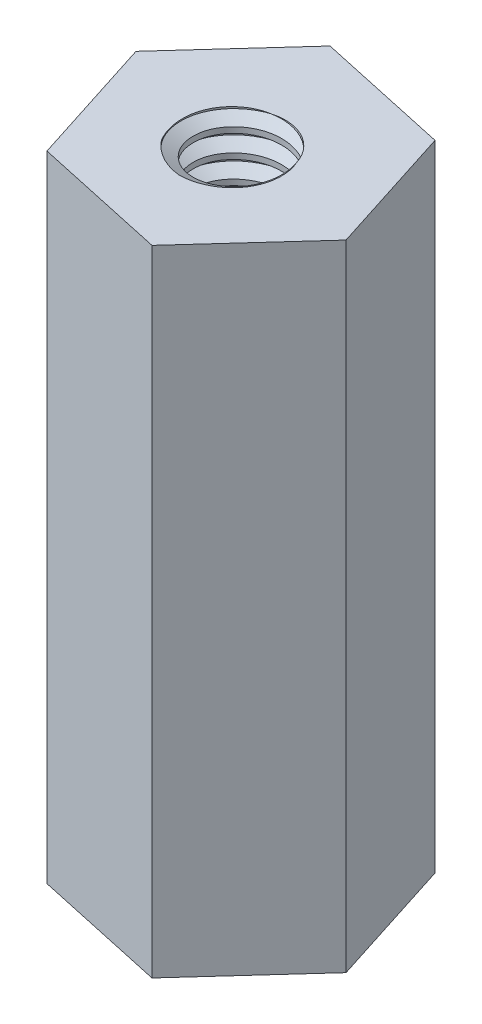
SolidWorks part; units mm, degrees
ref_plane "Front Plane" through (0, 0, 0) normal (0, 0, 1) x (1, 0, 0)
ref_plane "Top Plane" through (0, 0, 0) normal (0, 1, 0) x (1, 0, 0)
ref_plane "Right Plane" through (0, 0, 0) normal (1, 0, 0) x (0, 0, -1)
sketch "Sketch1" plane through (0, 0, 0) normal (0, 1, 0) x (1, 0, 0)
  line L1 (1.8496, 2.0346) -> (-0.8372, 2.6191)
  line L2 (-0.8372, 2.6191) -> (-2.6868, 0.5845)
  line L3 (-2.6868, 0.5845) -> (-1.8496, -2.0346)
  line L4 (-1.8496, -2.0346) -> (0.8372, -2.6191)
  line L5 (0.8372, -2.6191) -> (2.6868, -0.5845)
  line L6 (2.6868, -0.5845) -> (1.8496, 2.0346)
  circle A0 centre (0, 0) radius 2.3813 construction
  dimension "D1" = 4.7625
extrude "Boss-Extrude1" add sketch "Sketch1" along normal blind 12.7
hole_wizard "Tap Drill for #2-56 Tap1" positions "Sketch2" profile "Sketch3" hole size "#2-56" standard "ANSI Inch" end condition through all
sketch "Sketch2" plane through (0, 12.7, 0) normal (0, 1, 0) x (1, 0, 0)
  point P0 (0, 0)
sketch "Sketch3" plane through (0, 12.7, 0) normal (1, 0, 0) x (0, 0, 1)
  line L0 (0, 0) -> (0, 12.7)
  line L1 (0, 12.7) -> (0.889, 12.7)
  line L2 (0.889, 12.7) -> (0.889, 0)
  line L5 (0.889, 0) -> (0, 0)
  line L11 (0, -6.35) -> (0, 107.95) construction
  dimension "Thru Hole Dia." = 1.778
  dimension "Thru Hole Depth" = 12.7
thread "Thread1" pitch 0.4536 method cut profile "Thread Profile1" start angle 0, offset 1, length 0, pitch 0.4536, diameter 1.778
ref_plane "Plane1" through (-0.889, 13.7, 0) normal (0, 0, 1) x (-1, 0, 0)
sketch "Thread Profile1" plane through (-0.889, 13.7, 0) normal (0, 0, 1) x (-1, 0, 0)
  line L0 (0, 0) -> (0, 0.4536) construction
  line L1 (0, 0) -> (0.2455, 0.1417)
  line L2 (0.2455, 0.1417) -> (0.2455, 0.1984)
  line L3 (0.2455, 0.1984) -> (0, 0.3402)
  line L4 (0.2455, 0.1701) -> (0, 0.1701) construction
  line L11 (0, 0) -> (0, 0.3402)
  point P2 (0, 0)
  dimension "Pitch" = 0.4536
  dimension "Profile_Angle" = 60
  dimension "Profile_Land" = 0.0567
  dimension "Profile_Height" = 0.2455
